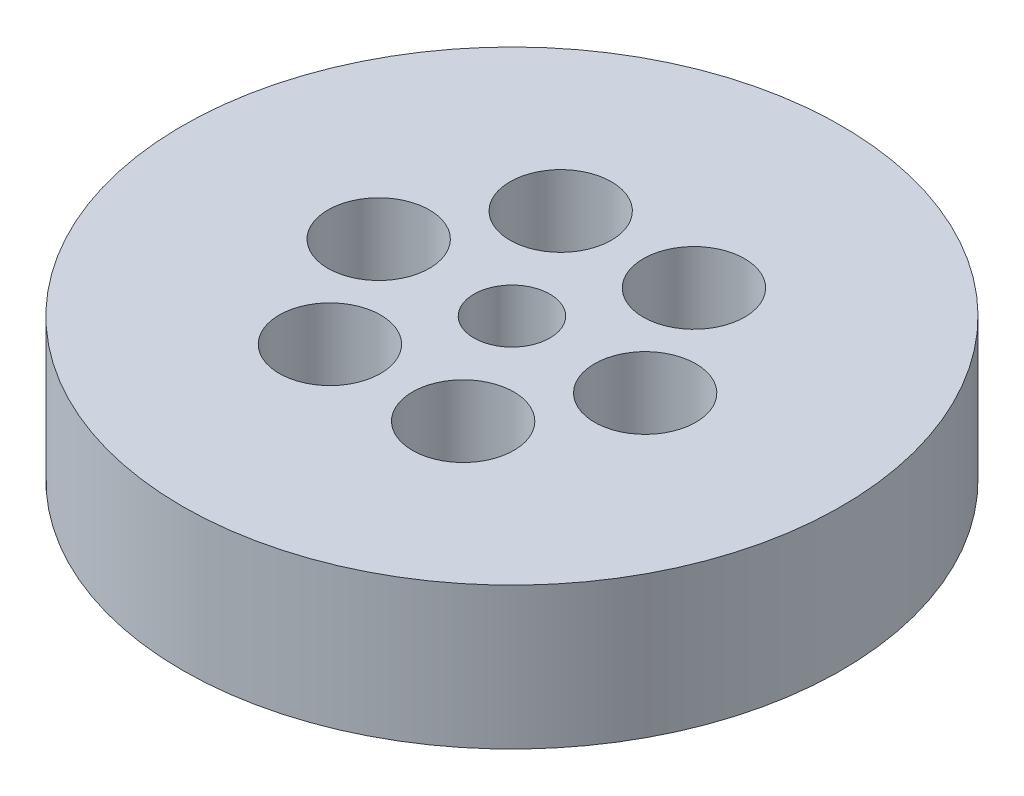
SolidWorks part; units mm, degrees
ref_plane "Front Plane" through (0, 0, 0) normal (0, 0, 1) x (1, 0, 0)
ref_plane "Top Plane" through (0, 0, 0) normal (0, 1, 0) x (1, 0, 0)
ref_plane "Right Plane" through (0, 0, 0) normal (1, 0, 0) x (0, 0, -1)
sketch "Sketch1" plane through (0, 0, 0) normal (0, 1, 0) x (1, 0, 0)
  circle A0 centre (0, 0) radius 65
  dimension "FLANGE_OD" = 130
extrude "Boss-Extrude1" add sketch "Sketch1" along normal blind 28
sketch "Sketch2" plane through (0, 0, 0) normal (0, 1, 0) x (1, 0, 0)
  circle A0 centre (0, 0) radius 7.5
  dimension "BORE_D" = 15
extrude "Cut-Extrude1" cut sketch "Sketch2" along normal through all
sketch "Sketch3" plane through (0, 28, 0) normal (0, 1, 0) x (1, 0, 0)
  circle A0 centre (0, 0) radius 26.2795 construction
  circle A1 centre (-26.2795, 0) radius 10
  dimension "BOLT_D" = 20
  dimension "BOLT_PCD" = 52.5589
extrude "Cut-Extrude2" cut sketch "Sketch3" against normal blind 27.486
pattern_circular "CirPattern1" count 6 over 360 about axis through (0, 0, 0) along (0, 1, 0) of "Cut-Extrude2"
